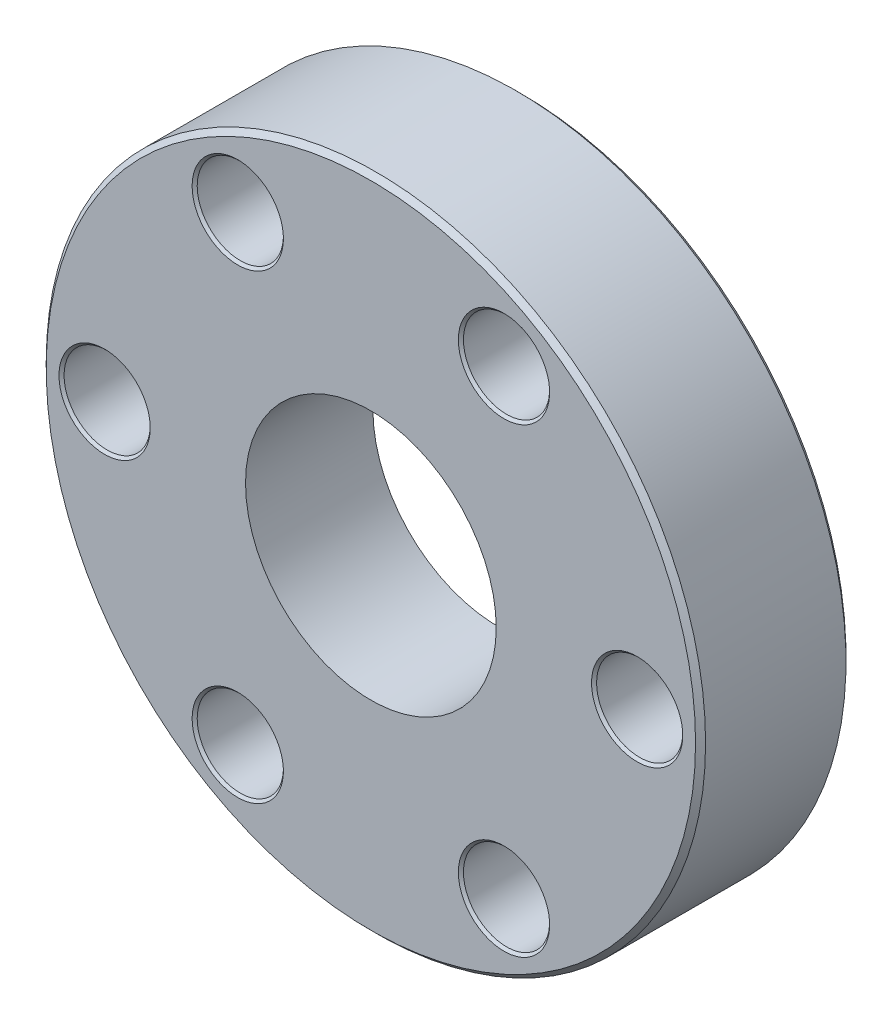
SolidWorks part; units mm, degrees
ref_plane "front" through (0, 0, 0) normal (0, 0, 1) x (1, 0, 0)
ref_plane "top" through (0, 0, 0) normal (0, 1, 0) x (1, 0, 0)
ref_plane "right" through (0, 0, 0) normal (1, 0, 0) x (0, 0, -1)
ref_axis "Axis1" through (0, 0, -4.6156) along (0, 0, 1)
sketch "Sketch1" plane through (0, 0, 0) normal (1, 0, 0) x (0, 0, -1)
  line L0 (0, 16.7005) -> (0, 10.795)
  line L1 (0, 10.795) -> (-0.9739, 10.795)
  line L2 (-0.9739, 10.795) -> (-0.6604, 9.017)
  line L3 (-0.6604, 9.017) -> (-1.1684, 9.017)
  line L4 (-1.1684, 9.017) -> (-1.1684, 6.35)
  line L5 (-1.1684, 6.35) -> (-7.62, 6.35)
  line L6 (-7.62, 6.35) -> (-7.62, 16.7005)
  line L7 (-7.62, 16.7005) -> (0, 16.7005)
  line L8 (0, 0) -> (-13.5387, 0) construction
  dimension "D1" = 12.7
  dimension "D2" = 1.1684
  dimension "D3" = 10
  dimension "D4" = 0.6604
  dimension "D5" = 21.59
  dimension "D6" = 18.034
  dimension "D7" = 7.62
  dimension "D8" = 33.401
revolve "Revolve1" add sketch "Sketch1" angle 360 about L8
chamfer "Chamfer1" distance 0.254 angle 45 2 edges at (-16.7005, 0, 0) (-16.7005, 0, 7.62)
hole_wizard "11/64 (0.17188) Diameter Hole2" positions "Sketch3" profile "Sketch2" hole size "11/64" standard "Ansi Inch" end condition up to next
sketch "Sketch3" plane through (0, 0, 0) normal (0, 0, 1) x (1, 0, 0)
  point P0 (13.4874, 0)
  dimension "D1" = 13.4874
sketch "Sketch2" plane through (13.4874, 0, 0) normal (1, 0, 0) x (0, 1, 0)
  line L0 (0, 0) -> (0, 7.62)
  line L1 (0, 7.62) -> (2.3114, 7.62)
  line L2 (2.1829, 7.4915) -> (2.1829, 0.1285)
  line L3 (2.1829, 0.1285) -> (2.3114, 0)
  line L5 (2.3114, 0) -> (0, 0)
  line L6 (-2.1829, 0.1285) -> (-2.3114, 0) construction
  line L7 (2.3114, 7.62) -> (2.1829, 7.4915)
  line L8 (-2.3114, 7.62) -> (-2.1829, 7.4915) construction
  line L11 (0, -6.35) -> (0, 107.95) construction
  dimension "Thru Hole Dia." = 4.3658
  dimension "Thru Hole Depth" = 7.62
  dimension "Near C'Sink Dia." = 4.6228
  dimension "Near C'Sink Angle" = 90
  dimension "Far C'Sink Dia." = 4.6228
  dimension "Far C'Sink Angle" = 90
pattern_circular "CirPattern1" count 6 over 360 about axis through (0, 0, -4.6156) along (0, 0, 1) of "11/64 (0.17188) Diameter Hole2"
